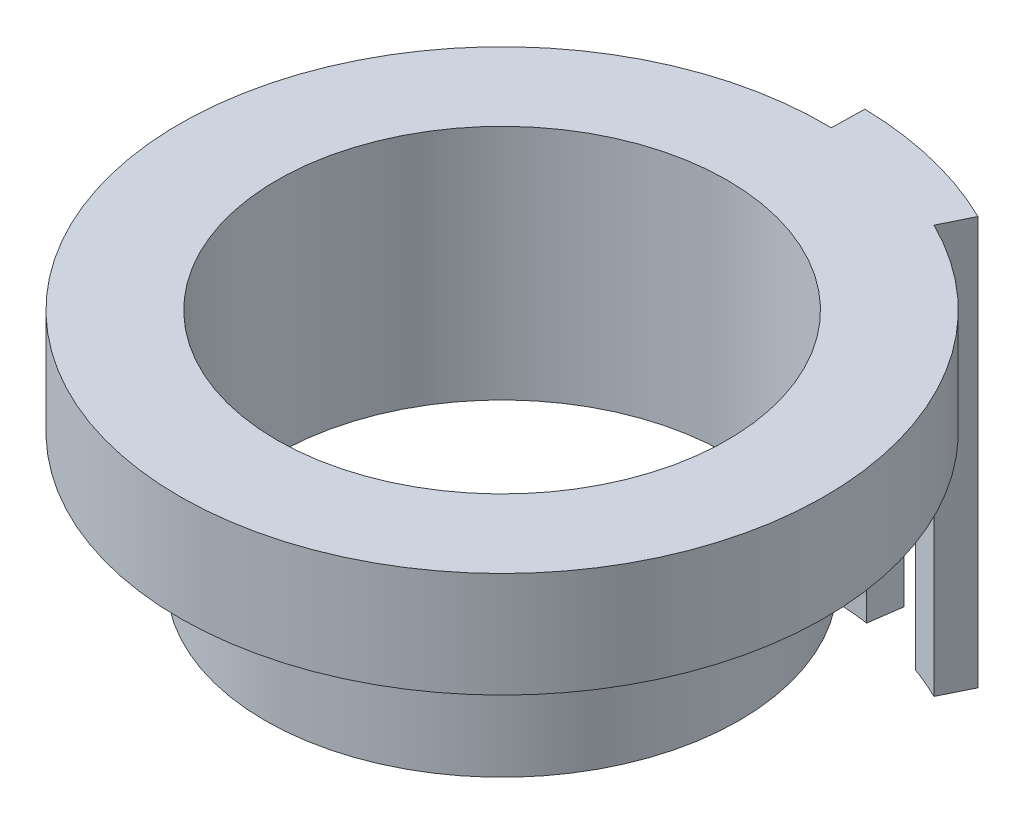
SolidWorks part; units mm, degrees
ref_plane "Front Plane" through (0, 0, 0) normal (0, 0, 1) x (1, 0, 0)
ref_plane "Top Plane" through (0, 0, 0) normal (0, 1, 0) x (1, 0, 0)
ref_plane "Right Plane" through (0, 0, 0) normal (1, 0, 0) x (0, 0, -1)
sketch "Sketch1" plane through (0, 0, 0) normal (0, 1, 0) x (1, 0, 0)
  circle A0 centre (0, 0) radius 24.5
  circle A1 centre (0, 0) radius 17.1
  circle A2 centre (0, 0) radius 18
  dimension "D1" = 49
  dimension "D2" = 34.2
  dimension "D3" = 36
extrude "Boss-Extrude1" add sketch "Sketch1" along normal blind 8 contours A2 A1 | A0 A2 region at (-23.807, 0, 0) region at (-17.4909, 0, 0)
extrude "Boss-Extrude2" add sketch "Sketch1<3>" against normal blind 10 contours A2 A1 region at (-17.4909, 0, 0)
sketch "Sketch1<3>" plane through (0, 0, 0) normal (0, 1, 0) x (1, 0, 0) same geometry as "Sketch1"
sketch "Sketch2" plane through (0, 8, 0) normal (0, 1, 0) x (1, 0, 0)
  line L0 (0.558, 26.9942) -> (0.5064, 24.4948)
  line L1 (11.914, 24.2292) -> (10.8109, 21.9858)
  line L2 (0, 0) -> (10.8109, 21.9858) construction
  line L3 (0, 0) -> (29.0171, 0) construction
  arc A0 (0.558, 26.9942) -> (11.914, 24.2292) centre (0, 0) cw
  circle A1 centre (0, 0) radius 24.5 construction
  arc A2 (0.5064, 24.4948) -> (10.8109, 21.9858) centre (0, 0) cw
  dimension "D1" = 27
  dimension "D2" = 25
  dimension "D3" = 63.816
extrude "Boss-Extrude3" add sketch "Sketch2" against normal blind 4
sketch "Sketch3" plane through (0, 4, 0) normal (0, -1, 0) x (1, 0, 0)
  line L0 (10.8109, -21.9858) -> (11.914, -24.2292) construction
  line L1 (0.558, -26.9942) -> (0.5064, -24.4948)
  line L2 (10.8109, -21.9858) -> (12.2161, -24.0783)
  line L3 (3.4278, -24.259) -> (3.7776, -26.7344)
  line L4 (8.3966, -23.0162) -> (9.2534, -25.3648)
  line L5 (3.6027, -25.4967) -> (8.825, -24.1905) construction
  line L6 (0, 0) -> (6.5514, -26.1931) construction
  arc A0 (0.5064, -24.4948) -> (10.8109, -21.9858) centre (0, 0) ccw
  arc A1 (0.5064, -24.4948) -> (10.8109, -21.9858) centre (0, 0) ccw construction
  circle A2 centre (0, 0) radius 24.5 construction
  arc A4 (0.558, -26.9942) -> (11.914, -24.2292) centre (0, 0) ccw construction
  arc A5 (0.558, -26.9942) -> (12.2161, -24.0783) centre (0, 0) ccw
  point P26 (6.2138, -24.8436)
  arc M8 (0.558, -26.9942) -> (11.914, -24.2292) centre (0, 0) ccw
  line M9 (11.914, -24.2292) -> (10.8109, -21.9858)
  arc M10 (10.8109, -21.9858) -> (0.5064, -24.4948) centre (0, 0) cw
  line M11 (0.5064, -24.4948) -> (0.558, -26.9942)
  dimension "D1" = 12
  dimension "D2" = 32.7
extrude "Boss-Extrude4" add sketch "Sketch3" along normal blind 27 contours L3 M10 M11 M8 | L4 M10 M8 M9 region at (2.0715, 4, -25.6714) region at (10.1113, 4, -23.6903)
